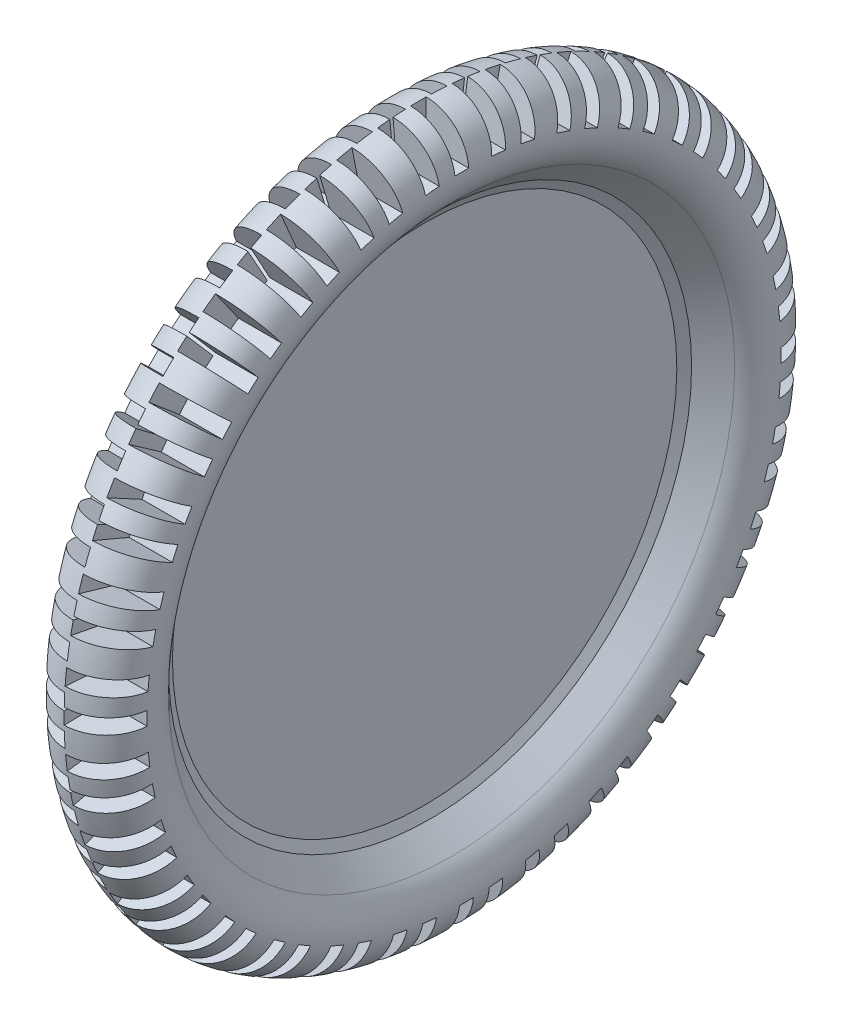
SolidWorks part; units mm, degrees
material "Plain Carbon Steel"
ref_plane "Front XY" through (0, 0, 0) normal (0, 0, 1) x (1, 0, 0)
ref_plane "Top XZ" through (0, 0, 0) normal (0, 1, 0) x (1, 0, 0)
ref_plane "Right YZ" through (0, 0, 0) normal (1, 0, 0) x (0, 0, -1)
sketch "Sketch2" plane through (0, 0, 0) normal (0, 1, 0) x (1, 0, 0)
  line L0 (0.5, 0) -> (-0.5, 0)
  line L1 (-0.5, 0) -> (-0.5, 35)
  line L2 (-0.5, 35) -> (-1.25, 36.299)
  line L4 (0, -0.1443) -> (0, 0.3097) construction
  line L6 (0.5, 35) -> (1.25, 36.299)
  line L7 (0.5, 0) -> (0.5, 35)
  line L8 (0.5, 0) -> (-49999.5, 0) construction
  line L9 (-1.25, 36.299) -> (-4.2426, 39.2917)
  line L10 (1.25, 36.299) -> (4.2426, 39.2917)
  arc A1 (4.2426, 39.2917) -> (-4.2426, 39.2917) centre (0, 43.5343) ccw
  point P16 (0, 0)
  dimension "D6" = 12
  dimension "D1" = 0.5
  dimension "D2" = 35
  dimension "D3" = 165
  dimension "D4" = 1.5
  dimension "D5" = 150
revolve "Revolve1" add sketch "Sketch2" angle 360 about L8
sketch "Sketch3" plane through (-0.5, 0, 0) normal (-1, 0, 0) x (0, 0, 1)
  line L0 (-3, 2.6458) -> (-3, -2.6458)
  circle A0 centre (0, 0) radius 6
  arc A1 (-3, -2.6458) -> (-3, 2.6458) centre (0, 0) ccw
  point P3 (4, 0)
  dimension "D1" = 12
  dimension "D2" = 8
  dimension "D3" = 7
extrude "Boss-Extrude1" add sketch "Sketch3" along normal blind 12
sketch "Sketch5" plane through (0, 0, 0) normal (1, 0, 0) x (0, 0, -1)
  line L0 (0, 0) -> (-5.8997, 67.4344) construction
  line L1 (-3.8349, 43.8326) -> (-4.3578, 49.8097)
  line L2 (0, 0) -> (5.8997, 67.4344) construction
  line L5 (0, 0) -> (-3.1098, 71.2267) construction
  line L6 (0, 3.6438) -> (0, 68.4077) construction
  line L7 (-2.181, 49.9524) -> (-1.9193, 43.9581)
  line L8 (0.7272, 49.9947) -> (0.6399, 43.9953)
  line L9 (-1.2797, 43.9814) -> (-1.4542, 49.9788)
  line L10 (3.6329, 49.8678) -> (3.197, 43.8837)
  line L11 (1.2797, 43.9814) -> (1.4542, 49.9788)
  line L12 (6.5263, 49.5722) -> (5.7432, 43.6236)
  line L13 (3.8349, 43.8326) -> (4.3578, 49.8097)
  arc A2 (-4.3578, 49.8097) -> (-2.181, 49.9524) centre (0, 0) cw
  arc A3 (-3.8349, 43.8326) -> (-1.9193, 43.9581) centre (0, 0) cw
  arc A4 (-1.2797, 43.9814) -> (0.6399, 43.9953) centre (0, 0) cw
  arc A5 (-1.4542, 49.9788) -> (0.7272, 49.9947) centre (0, 0) cw
  arc A6 (1.2797, 43.9814) -> (3.197, 43.8837) centre (0, 0) cw
  arc A7 (1.4542, 49.9788) -> (3.6329, 49.8678) centre (0, 0) cw
  arc A8 (3.8349, 43.8326) -> (5.7432, 43.6236) centre (0, 0) cw
  arc A9 (4.3578, 49.8097) -> (6.5263, 49.5722) centre (0, 0) cw
  point P26 (0, 0)
  dimension "D3" = 44
  dimension "D4" = 50
  dimension "D1" = 5
  dimension "D2" = 2.5
  dimension "D5" = 4
extrude "Cut-Extrude1" cut sketch "Sketch5" against normal through all contours A2 L7 A3 L1 | A7 L10 A6 L11
extrude "Cut-Extrude2" cut sketch "Sketch5<3>" along normal through all contours A5 L8 A4 L9 | A9 L12 A8 L13
sketch "Sketch5<3>" plane through (0, 0, 0) normal (1, 0, 0) x (0, 0, -1) same geometry as "Sketch5"
pattern_circular "CirPattern1" count 30 over 360 about axis through (0.5, 0, 0) along (-1, 0, 0) of "Cut-Extrude1", "Cut-Extrude2"
